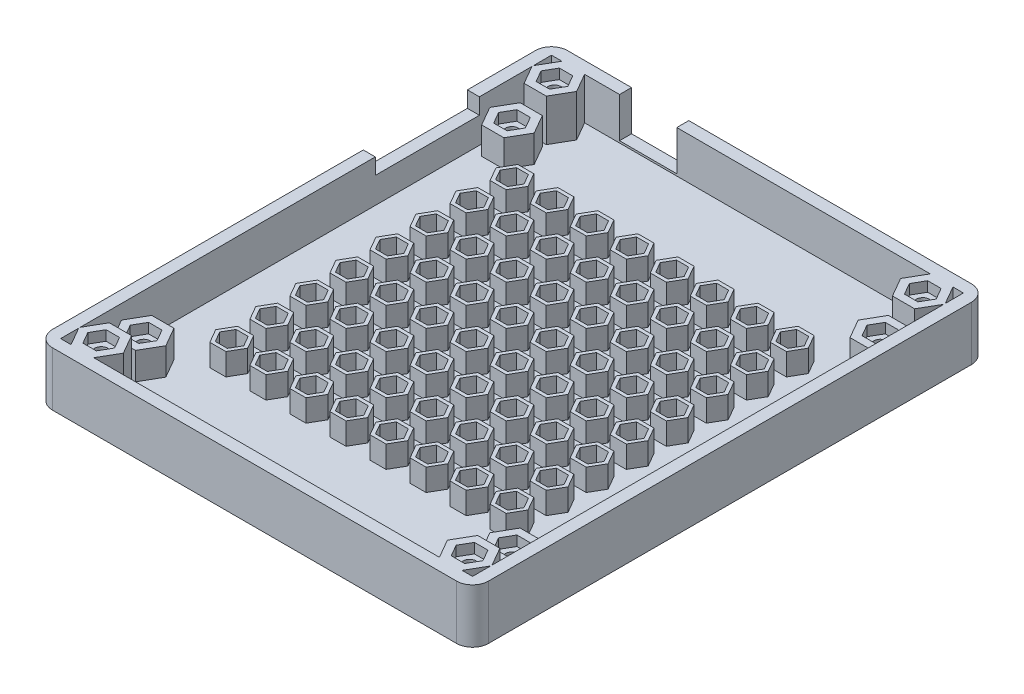
SolidWorks part; units mm, degrees
ref_plane "Přední rovina" through (0, 0, 0) normal (0, 0, 1) x (1, 0, 0)
ref_plane "Horní rovina" through (0, 0, 0) normal (0, 1, 0) x (1, 0, 0)
ref_plane "Pravá rovina" through (0, 0, 0) normal (1, 0, 0) x (0, 0, -1)
sketch "Skica1" plane through (0, 0, 0) normal (0, 1, 0) x (1, 0, 0)
  line L0 (0, 0) -> (-100, 100) construction
  line L1 (-50, 50) -> (50, 50) construction
  line L2 (-50, 50) -> (-50, -50) construction
  line L3 (-50, -50) -> (50, -50) construction
  line L4 (50, 50) -> (50, -50) construction
  line L5 (-50, 50) -> (50, -50) construction
  line L6 (-50, -50) -> (50, 50) construction
  line L7 (-47.6743, 43.1) -> (-44.3257, 43.1)
  line L8 (-44.3257, 43.1) -> (-42.6514, 46)
  line L9 (-42.6514, 46) -> (-44.3257, 48.9)
  line L10 (-44.3257, 48.9) -> (-47.6743, 48.9)
  line L11 (-47.6743, 48.9) -> (-49.3486, 46)
  line L12 (-49.3486, 46) -> (-47.6743, 43.1)
  line L13 (-48.7713, 41.2) -> (-43.2287, 41.2)
  line L14 (-43.2287, 41.2) -> (-40.4574, 46)
  line L15 (-40.4574, 46) -> (-43.2287, 50.8)
  line L16 (-43.2287, 50.8) -> (-48.7713, 50.8)
  line L17 (-48.7713, 50.8) -> (-51.5426, 46)
  line L18 (-51.5426, 46) -> (-48.7713, 41.2)
  line L19 (0, 81.3987) -> (0, -91.9033) construction
  line L20 (-42.6514, 56.6) -> (-44.3257, 59.5)
  line L21 (-44.3257, 59.5) -> (-47.6743, 59.5)
  line L22 (-47.6743, 59.5) -> (-49.3486, 56.6)
  line L23 (-49.3486, 56.6) -> (-47.6743, 53.7)
  line L24 (-47.6743, 53.7) -> (-44.3257, 53.7)
  line L25 (-44.3257, 53.7) -> (-42.6514, 56.6)
  line L26 (-48.7713, 51.8) -> (-43.2287, 51.8)
  line L27 (-43.2287, 51.8) -> (-40.4574, 56.6)
  line L28 (-40.4574, 56.6) -> (-43.2287, 61.4)
  line L29 (-43.2287, 61.4) -> (-48.7713, 61.4)
  line L30 (-48.7713, 61.4) -> (-51.5426, 56.6)
  line L31 (-51.5426, 56.6) -> (-48.7713, 51.8)
  line L36 (74.9355, -74.9355) -> (-74.9355, 74.9355) construction
  line L37 (74.9355, 74.9355) -> (-74.9355, -74.9355) construction
  line L38 (-54.4426, -64.3) -> (54.4426, -64.3)
  line L39 (-54.4426, -64.3) -> (-54.4426, 64.3)
  line L40 (-54.4426, 64.3) -> (54.4426, 64.3)
  line L41 (54.4426, -64.3) -> (54.4426, 64.3)
  line L42 (-54.4426, -64.3) -> (54.4426, 64.3) construction
  line L43 (-54.4426, 64.3) -> (54.4426, -64.3) construction
  line L44 (-106.951, 0) -> (125.2961, 0) construction
  line L45 (-46, 37.8836) -> (-46, 68.4593) construction
  line L47 (-51.4426, -61.3) -> (51.4426, -61.3)
  line L48 (-51.4426, -61.3) -> (-51.4426, 61.3)
  line L49 (-51.4426, 61.3) -> (51.4426, 61.3)
  line L50 (51.4426, -61.3) -> (51.4426, 61.3)
  line L51 (-51.4426, -61.3) -> (51.4426, 61.3) construction
  line L52 (-51.4426, 61.3) -> (51.4426, -61.3) construction
  circle A0 centre (-46, 46) radius 2.9 construction
  circle A1 centre (-46, 46) radius 4.8 construction
  circle A2 centre (-46, 56.6) radius 2.9 construction
  circle A3 centre (-46, 56.6) radius 4.8 construction
  circle A4 centre (-46, 46) radius 1.6
  circle A5 centre (-46, 56.6) radius 1.6
  point P0 (0, 0)
  point P7 (-41.8431, 43.6)
  dimension "D9" = 3
  dimension "D10" = 3
  dimension "D11" = 0.1
  dimension "D12" = 0.1
  dimension "D13" = 3.2
  dimension "D14" = 3.2
  dimension "D1" = 100
  dimension "D2" = 100
  dimension "D3" = 5.8
  dimension "D4" = 4
  dimension "D5" = 9.6
  dimension "D6" = 5.8
  dimension "D7" = 9.6
  dimension "D8" = 1
extrude "Přidat vysunutím25" add sketch "Skica1" against normal blind 3 contours L49 L48 L30 | L20 L21 L22 L23 L24 L25 | L7 L8 L9 L10 L11 L12 | L48 L47 L50 L49 | L13 L14 L15 L16 L17 L18 | L26 L27 L28 L29 L30 L31 region at (-50.5714, 0, -59.7911)
extrude "Přidat vysunutím26" add sketch "Skica1<21>" against normal blind 3 and the other way blind 10.5 contours L38 L41 L40 L39 L50 L47 L48 L18 L17 L31 L30 L49 L29 L28 | L18 L48 L17 | L31 L48 L30 | L30 L49 L28 L29 region at (-51.4759, 0, -46) region at (-51.4759, 0, -56.6) region at (-46, 0, -61.3498) region at (-52.7575, 0, 0)
sketch "Skica1<21>" plane through (0, 0, 0) normal (0, 1, 0) x (1, 0, 0) same geometry as "Skica1"
extrude "Přidat vysunutím28" add sketch "Skica1<23>" along normal blind 6.8 contours L48 L18 L13 L14 L15 L16 L17 L12 L11 L10 L9 L8 L7 | L18 L48 L17 region at (-49.9806, 0, -43.5863) region at (-51.4759, 0, -46)
sketch "Skica1<23>" plane through (0, 0, 0) normal (0, 1, 0) x (1, 0, 0) same geometry as "Skica1"
extrude "Přidat vysunutím29" add sketch "Skica1<24>" along normal blind 4.3 contours L11 L12 L7 L8 L9 L10 region at (-48.4347, 0, -44.5943)
sketch "Skica1<24>" plane through (0, 0, 0) normal (0, 1, 0) x (1, 0, 0) same geometry as "Skica1"
pattern_linear "LinPole3" count 2 spacing 92 along (1, 0, 0) count 2 spacing 92 along (0, 0, 1) of "Přidat vysunutím28", "Přidat vysunutím29"
extrude "Přidat vysunutím30" add sketch "Skica1<25>" along normal blind 10.5 contours L49 L30 L48 L31 L26 L27 L28 L25 L24 L23 L22 L21 L20 | L30 L49 L28 L29 | L31 L48 L30 region at (-51.2973, 0, -56.6) region at (-51.4759, 0, -56.6) region at (-46, 0, -61.3498)
sketch "Skica1<25>" plane through (0, 0, 0) normal (0, 1, 0) x (1, 0, 0) same geometry as "Skica1"
extrude "Přidat vysunutím31" add sketch "Skica1<26>" along normal blind 8 contours L24 L25 L20 L21 L22 L23 A5 region at (-43.5653, 0, -55.1943)
sketch "Skica1<26>" plane through (0, 0, 0) normal (0, 1, 0) x (1, 0, 0) same geometry as "Skica1"
pattern_linear "LinPole4" count 2 spacing 92 along (1, 0, 0) count 2 spacing 113.2 along (0, 0, 1) of "Přidat vysunutím31", "Přidat vysunutím30"
fillet "Zaoblit4" radius 4 4 edges at (-54.4426, 3.75, 64.3) (54.4426, 3.75, 64.3) (54.4426, 3.75, -64.3) (-54.4426, 3.75, -64.3)
sketch "Skica9" plane through (-54.4426, 0, 0) normal (-1, 0, 0) x (0, 0, 1)
  line L0 (60.3, 10.5) -> (-60.3, 10.5) construction
  line L1 (-17.3, 6.5) -> (-43.3, 6.5)
  line L2 (-17.3, 6.5) -> (-17.3, 10.5)
  line L3 (-17.3, 10.5) -> (-43.3, 10.5)
  line L4 (-43.3, 6.5) -> (-43.3, 10.5)
  line L5 (-17.3, 6.5) -> (-43.3, 10.5) construction
  line L6 (-17.3, 10.5) -> (-43.3, 6.5) construction
  line L7 (-64.3, -3) -> (-64.3, 10.5) construction
  point P0 (-30.3, 8.5)
  dimension "D1" = 26
  dimension "D2" = 21
  dimension "D3" = 4
extrude "Odebrat vysunutím1" cut sketch "Skica9" against normal blind 4 contours L4 L3 L2 L1
sketch "Skica10" plane through (0, 0, -64.3) normal (0, 0, -1) x (-1, 0, 0)
  line L0 (50.4426, 10.5) -> (-50.4426, 10.5) construction
  line L1 (20.1426, 0.5) -> (34.4426, 0.5)
  line L2 (20.1426, 0.5) -> (20.1426, 10.5)
  line L3 (20.1426, 10.5) -> (34.4426, 10.5)
  line L4 (34.4426, 0.5) -> (34.4426, 10.5)
  line L5 (54.4426, 10.5) -> (54.4426, -3) construction
  dimension "D1" = 10
  dimension "D2" = 14.3
  dimension "D3" = 20
extrude "Odebrat vysunutím2" cut sketch "Skica10" against normal blind 5
sketch "Skica11" plane through (0, 0, 0) normal (0, 1, 0) x (1, 0, 0)
  line L0 (-43.171, 61.3) -> (43.171, 61.3) construction
  line L1 (-35, -35) -> (35, -35) construction
  line L2 (-35, -35) -> (-35, 35) construction
  line L3 (-35, 35) -> (35, 35) construction
  line L4 (35, -35) -> (35, 35) construction
  line L5 (-35, -35) -> (35, 35) construction
  line L6 (-35, 35) -> (35, -35) construction
  line L7 (-33.5, 32.4019) -> (-32, 35)
  line L8 (-32, 35) -> (-33.5, 37.5981)
  line L9 (-33.5, 37.5981) -> (-36.5, 37.5981)
  line L10 (-36.5, 37.5981) -> (-38, 35)
  line L11 (-38, 35) -> (-36.5, 32.4019)
  line L12 (-36.5, 32.4019) -> (-33.5, 32.4019)
  line L13 (-33, 31.5359) -> (-31, 35)
  line L14 (-31, 35) -> (-33, 38.4641)
  line L15 (-33, 38.4641) -> (-37, 38.4641)
  line L16 (-37, 38.4641) -> (-39, 35)
  line L17 (-39, 35) -> (-37, 31.5359)
  line L18 (-37, 31.5359) -> (-33, 31.5359)
  circle A0 centre (-35, 35) radius 2.5981 construction
  circle A1 centre (-35, 35) radius 3.4641 construction
  point P0 (0, 0)
  dimension "D1" = 70
  dimension "D2" = 3
  dimension "D3" = 4
extrude "Přidat vysunutím32" add sketch "Skica11" along normal blind 5.5
pattern_linear "LinPole5" count 8 spacing 10 along (1, 0, 0) count 8 spacing 10 along (0, 0, 1) of "Přidat vysunutím32"
